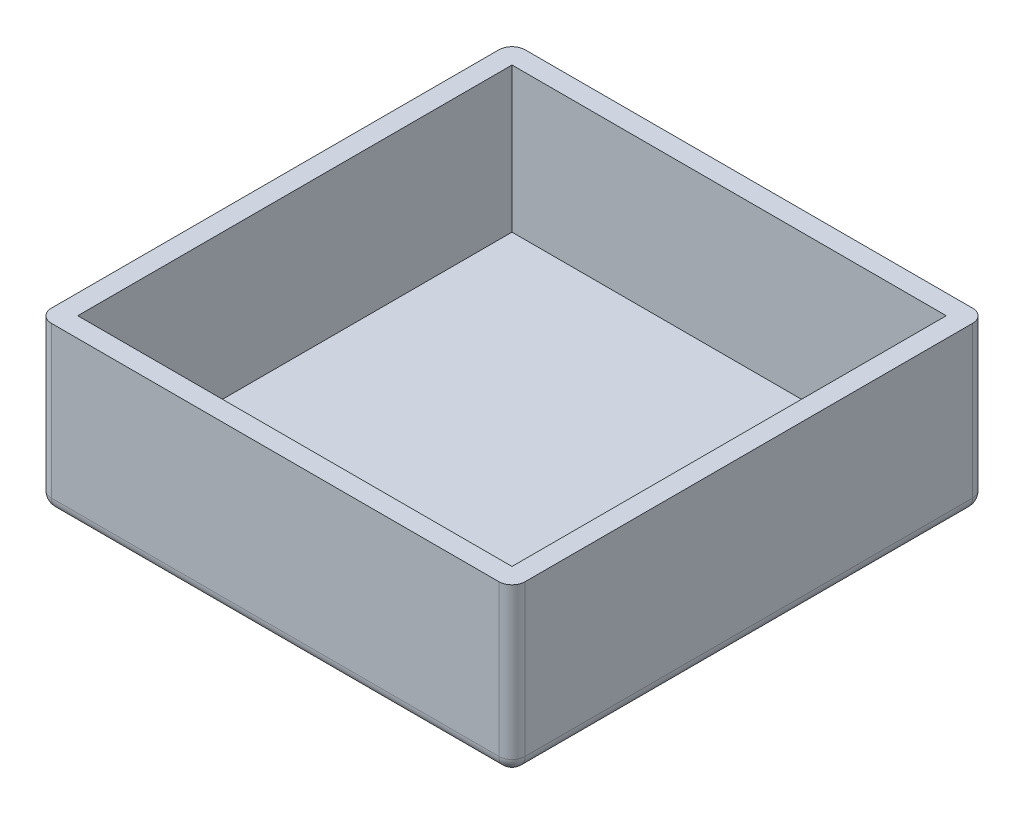
SolidWorks part; units mm, degrees
ref_plane "前视基准面" through (0, 0, 0) normal (0, 0, 1) x (1, 0, 0)
ref_plane "上视基准面" through (0, 0, 0) normal (0, 1, 0) x (1, 0, 0)
ref_plane "右视基准面" through (0, 0, 0) normal (1, 0, 0) x (0, 0, -1)
other "Configuration Table"
sketch "草图1" plane through (0, 0, 0) normal (0, 1, 0) x (1, 0, 0)
  line L1 (-33, 33) -> (33, 33)
  line L2 (-33, 33) -> (-33, -33)
  line L3 (-33, -33) -> (33, -33)
  line L4 (33, 33) -> (33, -33)
  line L5 (-33, 33) -> (33, -33) construction
  line L6 (-33, -33) -> (33, 33) construction
  point P0 (0, 0)
  dimension "D1" = 66
  dimension "D2" = 66
extrude "凸台-拉伸1" add sketch "草图1" along normal blind 3
extrude "拉伸-薄壁1" add sketch "草图1<2>" along normal blind 25 thin thin type one direction wall 3
sketch "草图1<2>" plane through (0, 0, 0) normal (0, 1, 0) x (1, 0, 0) same geometry as "草图1"
fillet "圆角1" radius 2 8 edges at (36, 0, 0) (0, 0, 36) (-36, 0, 0) (0, 0, -36) (-36, 12.5, -36) (36, 12.5, -36) (36, 12.5, 36) (-36, 12.5, 36)
